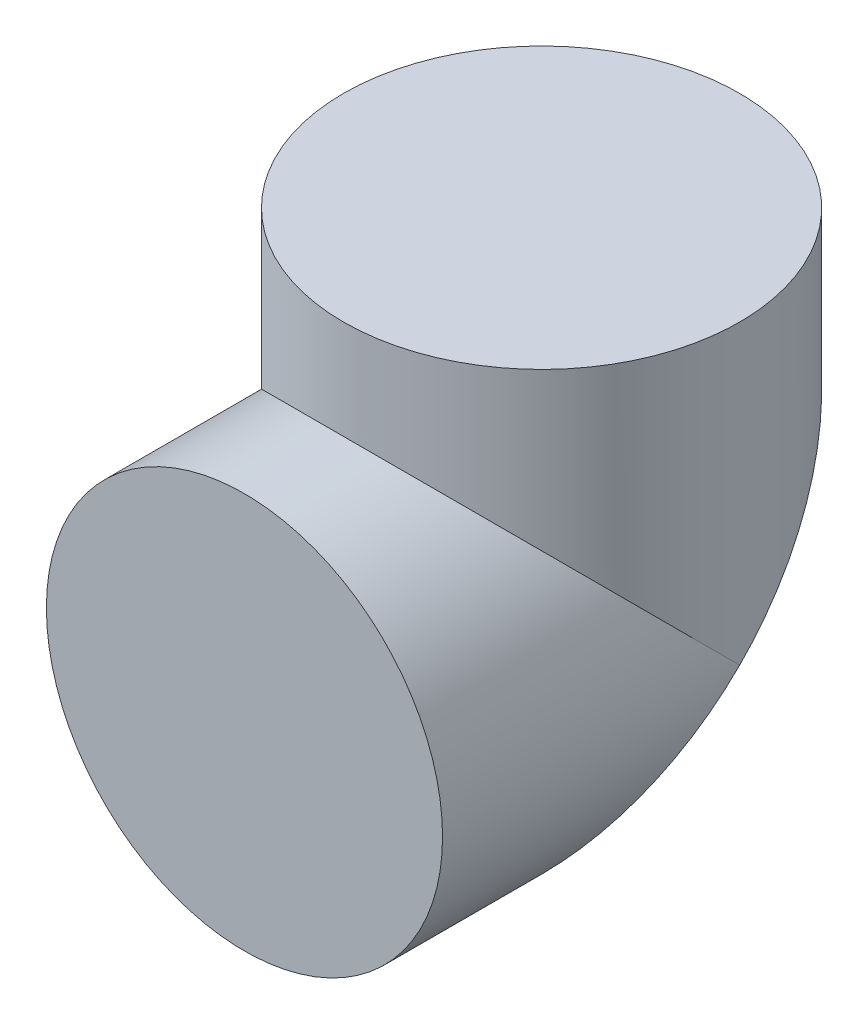
SolidWorks part; units mm, degrees
ref_plane "前视基准面" through (0, 0, 0) normal (0, 0, 1) x (1, 0, 0)
ref_plane "上视基准面" through (0, 0, 0) normal (0, 1, 0) x (1, 0, 0)
ref_plane "右视基准面" through (0, 0, 0) normal (1, 0, 0) x (0, 0, -1)
other "Configuration Table"
sketch "草图3" plane through (0, 0, 0) normal (0, 1, 0) x (1, 0, 0)
  circle A1 centre (0, -20) radius 20
extrude "凸台-拉伸2" add sketch "草图3" along normal blind 50
sketch "草图4" plane through (0, 0, 0) normal (0, 0, 1) x (1, 0, 0)
  circle A1 centre (0, 20) radius 20
extrude "凸台-拉伸3" add sketch "草图4" along normal blind 50
sketch "草图5" plane through (0, 0, 0) normal (1, 0, 0) x (0, 0, -1)
  line L0 (0, 40) -> (-40, 0)
  line L1 (-40, 0) -> (-40, -16.7973)
  line L2 (-40, -16.7973) -> (11.41, -16.7973)
  line L3 (11.41, -16.7973) -> (0, 40)
extrude "切除-拉伸1" cut sketch "草图5" against normal blind 40
sketch "草图6" plane through (0, 0, 0) normal (-1, 0, 0) x (0, 0, 1)
  line L0 (0, 40) -> (40, 0)
  line L1 (40, 0) -> (42.8401, -18.1759)
  line L2 (42.8401, -18.1759) -> (-20.8977, -9.0879)
  line L3 (-20.8977, -9.0879) -> (0, 40)
extrude "切除-拉伸2" cut sketch "草图6" against normal blind 40
ref_point "点2"
ref_point "点6"
sketch "草图7" plane through (0, 0, 50) normal (0, 0, 1) x (1, 0, 0)
  line L0 (0, 20) -> (0, 40)
  circle A0 centre (0, 20) radius 20 construction
sketch "草图8" plane through (0, 50, 0) normal (0, 1, 0) x (1, 0, 0)
  line L2 (0, -20) -> (0, -40)
  arc A0 (-20, -20) -> (20, -20) centre (0, -20) ccw construction
ref_axis "基准轴1" through (0, 20, 50) along (0, 0, 1)
ref_axis "基准轴2" through (0, 20, 50) along (0, 1, 0)
ref_axis "基准轴3" through (0, 50, 20) along (0, 1, 0)
ref_axis "基准轴4" through (0, 50, 20) along (0, 0, 1)
